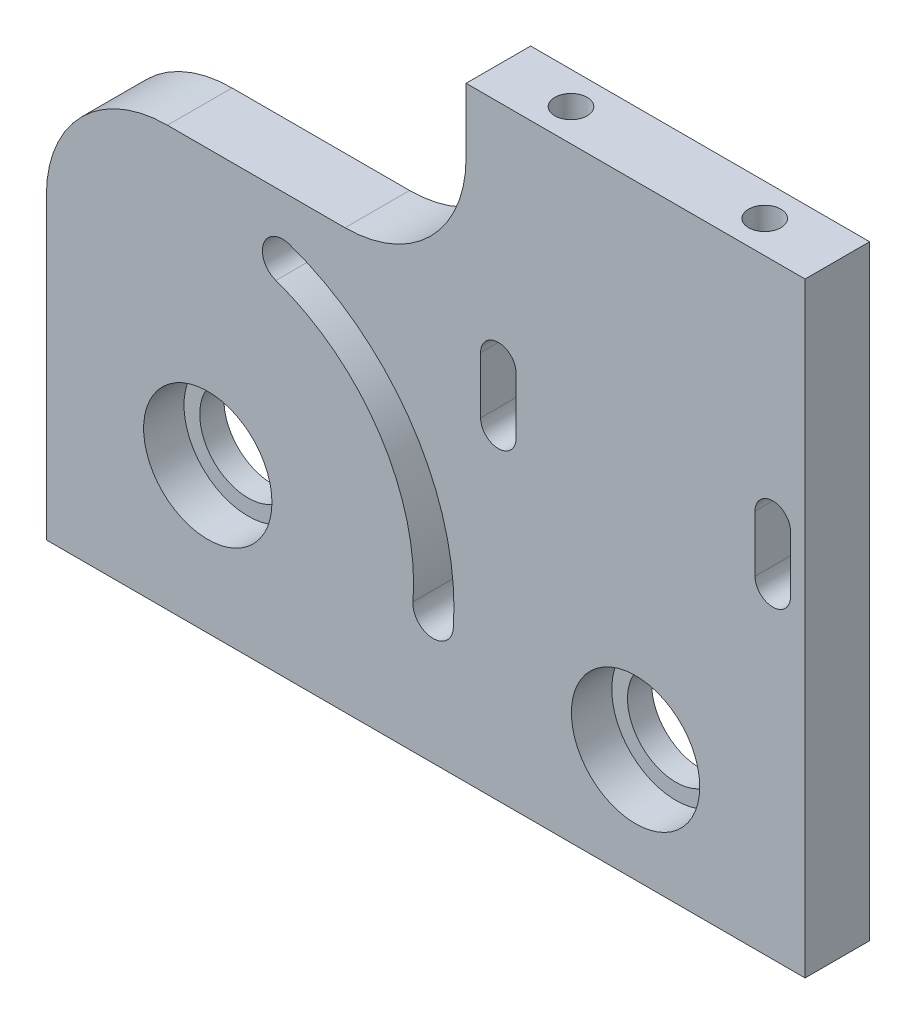
SolidWorks part; units mm, degrees
material "Alliage 1060"
ref_plane "Plan de face" through (0, 0, 0) normal (0, 0, 1) x (1, 0, 0)
ref_plane "Plan de dessus" through (0, 0, 0) normal (0, 1, 0) x (1, 0, 0)
ref_plane "Plan de droite" through (0, 0, 0) normal (1, 0, 0) x (0, 0, -1)
sketch "Esquisse1" plane through (0, 0, 0) normal (0, 0, 1) x (1, 0, 0)
  line L1 (0, 0) -> (114.433, 0)
  line L2 (0, 0) -> (0, 75)
  line L3 (0, 75) -> (114.433, 75)
  line L4 (114.433, 0) -> (114.433, 75)
  dimension "D1" = 75
extrude "Boss.-Extru.1" add sketch "Esquisse1" along normal blind 8
sketch "Esquisse2" plane through (0, 0, 8) normal (0, 0, 1) x (1, 0, 0)
  line L0 (20, 18) -> (20, 0) construction
  line L1 (0, 0) -> (114.433, 0) construction
  line L2 (20, 18) -> (0, 18) construction
  line L3 (0, 75) -> (0, 0) construction
  line L4 (20, 18) -> (73, 14) construction
  circle A0 centre (20, 18) radius 7.95
  circle A1 centre (73, 14) radius 7.95
  dimension "D1" = 15.9
  dimension "D2" = 18
  dimension "D3" = 20
  dimension "D4" = 53
  dimension "D5" = 14
extrude "Enlèv. mat.-Extru.1" cut sketch "Esquisse2" against normal blind 5
sketch "Esquisse3" plane through (0, 0, 3) normal (0, 0, 1) x (1, 0, 0)
  circle A0 centre (20, 18) radius 6
  circle A1 centre (73, 14) radius 6
  dimension "D1" = 12
extrude "Enlèv. mat.-Extru.2" cut sketch "Esquisse3" against normal up to next
sketch "Esquisse4" plane through (0, 0, 8) normal (0, 0, 1) x (1, 0, 0)
  line L0 (20, 18) -> (47.9206, 15.8928) construction
  line L1 (47.9206, 15.8928) -> (73, 14) construction
  line L2 (20, 18) -> (29.2618, 44.4238) construction
  arc A0 (29.2618, 44.4238) -> (47.9206, 15.8928) centre (20, 18) cw construction
  arc A1 (50.4135, 15.7046) -> (30.0887, 46.7831) centre (20, 18) ccw
  arc A2 (45.4277, 16.0809) -> (28.4348, 42.0646) centre (20, 18) ccw
  arc A3 (45.4277, 16.0809) -> (50.4135, 15.7046) centre (47.9206, 15.8928) ccw
  arc A4 (30.0887, 46.7831) -> (28.4348, 42.0646) centre (29.2618, 44.4238) ccw
  point P7 (43.4337, 33.3252)
  dimension "D4" = 2.5
  dimension "D2" = 75
  dimension "D3" = 28
extrude "Enlèv. mat.-Extru.3" cut sketch "Esquisse4" against normal through all
sketch "Esquisse5" plane through (0, 0, 8) normal (0, 0, 1) x (1, 0, 0)
  line L0 (114.433, 75) -> (0, 75) construction
  line L1 (114.433, 0) -> (94, 0)
  line L2 (114.433, 0) -> (114.433, 75)
  line L3 (114.433, 75) -> (94, 75)
  line L4 (94, 0) -> (94, 75)
  circle A0 centre (73, 14) radius 6 construction
  dimension "D1" = 21
extrude "Enlèv. mat.-Extru.4" cut sketch "Esquisse5" against normal through all
sketch "Esquisse6" plane through (0, 0, 8) normal (0, 0, 1) x (1, 0, 0)
  line L0 (56, 40) -> (90, 40) construction
  line L1 (0, 0) -> (94, 0) construction
  line L2 (94, 75) -> (94, 0) construction
  line L3 (90, 40) -> (90, 47) construction
  line L4 (87.8, 40) -> (87.8, 47)
  line L5 (92.2, 40) -> (92.2, 47)
  line L6 (73, 40) -> (73, 42.9196) construction
  line L7 (56, 40) -> (56, 47) construction
  line L8 (58.2, 40) -> (58.2, 47)
  line L9 (53.8, 40) -> (53.8, 47)
  arc A2 (87.8, 40) -> (92.2, 40) centre (90, 40) ccw
  arc A3 (92.2, 47) -> (87.8, 47) centre (90, 47) ccw
  arc A4 (58.2, 40) -> (53.8, 40) centre (56, 40) cw
  arc A5 (53.8, 47) -> (58.2, 47) centre (56, 47) cw
  point P1 (90, 43.5)
  point P15 (56, 43.5)
  dimension "D3" = 4.4
  dimension "D1" = 40
  dimension "D2" = 4
  dimension "D4" = 34
  dimension "D5" = 7
extrude "Enlèv. mat.-Extru.5" cut sketch "Esquisse6" against normal through all
sketch "Esquisse7" plane through (0, 0, 8) normal (0, 0, 1) x (1, 0, 0)
  line L0 (0, 75) -> (0, 0) construction
  line L1 (52, 75) -> (0, 75)
  line L2 (52, 75) -> (52, 52)
  line L3 (52, 52) -> (0, 52)
  line L4 (0, 75) -> (0, 52)
  line L5 (94, 75) -> (94, 0) construction
  line L6 (0, 0) -> (94, 0) construction
  line L7 (94, 75) -> (0, 75) construction
  dimension "D1" = 42
  dimension "D2" = 52
extrude "Enlèv. mat.-Extru.6" cut sketch "Esquisse7" against normal through all
sketch "Esquisse10" plane through (0, 75, 0) normal (0, 1, 0) x (1, 0, 0)
  line L0 (85, -4) -> (61, -4) construction
  line L1 (94, 0) -> (94, -8) construction
  circle A0 centre (85, -4) radius 2
  circle A1 centre (61, -4) radius 2
  point P6 (94, -4)
  dimension "D1" = 4
  dimension "D2" = 24
  dimension "D3" = 9
extrude "Enlèv. mat.-Extru.7" cut sketch "Esquisse10" against normal blind 30
fillet "Congé1" radius 15 2 edges at (52, 52, 4) (0, 52, 4)
sketch "Esquisse11" plane through (0, 0, 0) normal (0, -1, 0) x (1, 0, 0)
  line L0 (94, 0) -> (94, 8) construction
  line L1 (6, 4) -> (88, 4) construction
  line L2 (0, 8) -> (94, 8) construction
  line L3 (0, 8) -> (0, 0) construction
  circle A0 centre (6, 4) radius 2
  circle A1 centre (88, 4) radius 2
  point P8 (47, 8)
  point P9 (47, 4)
  point P12 (0, 4)
  dimension "D1" = 4
  dimension "D2" = 6
extrude "Enlèv. mat.-Extru.8" cut sketch "Esquisse11" against normal blind 20
